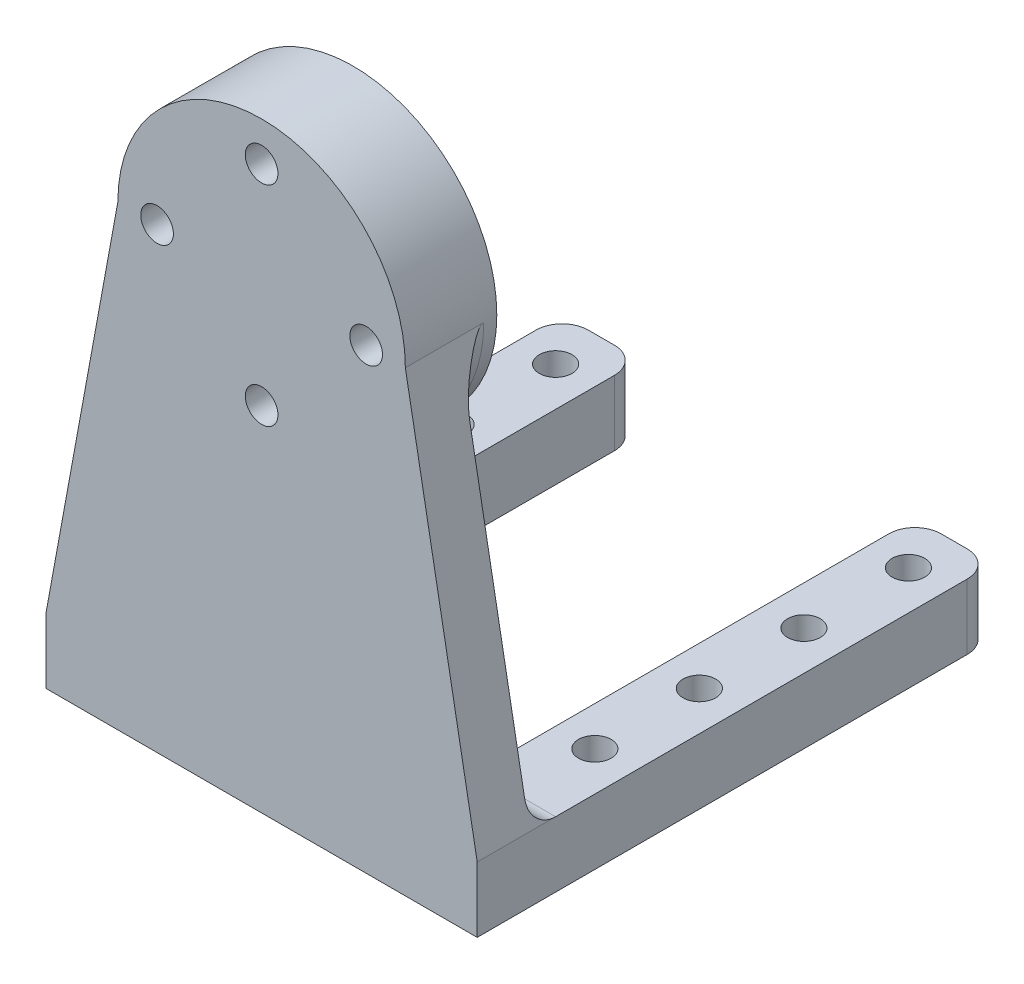
SolidWorks part; units mm, degrees
ref_plane "Plan de face" through (0, 0, 0) normal (0, 0, 1) x (1, 0, 0)
ref_plane "Plan de dessus" through (0, 0, 0) normal (0, 1, 0) x (1, 0, 0)
ref_plane "Plan de droite" through (0, 0, 0) normal (1, 0, 0) x (0, 0, -1)
sketch "Esquisse1" plane through (0, 0, 0) normal (0, 0, 1) x (1, 0, 0)
  circle A0 centre (0, 0) radius 11
  dimension "D1" = 22
extrude "Boss.-Extru.1" add sketch "Esquisse1" along normal blind 7
sketch "Esquisse2" plane through (0, 0, 7) normal (0, 0, 1) x (1, 0, 0)
  line L0 (0, 0) -> (8, 0) construction
  circle A0 centre (8, 0) radius 1.25
  circle A1 centre (0, -8) radius 1.25
  circle A2 centre (-8, 0) radius 1.25
  circle A3 centre (0, 8) radius 1.25
  point P13 (0, 0)
  dimension "D2" = 2.5
  dimension "D1" = 8
extrude "Enlèv. mat.-Extru.1" cut sketch "Esquisse2" against normal through all
sketch "Esquisse3" plane through (0, 0, 7) normal (0, 0, 1) x (1, 0, 0)
  line L0 (-11, 0) -> (-11, -35) construction
  line L1 (-11, -35) -> (11, -35)
  line L2 (11, -35) -> (11, 0) construction
  line L4 (-16.5, -35) -> (-11, -35)
  line L5 (11, -35) -> (16.5, -35)
  line L7 (-16.5, -35) -> (-16.5, -30)
  line L8 (-16.5, -30) -> (-11, 0)
  line L9 (11, 0) -> (16.5, -30)
  line L10 (16.5, -30) -> (16.5, -35)
  circle A0 centre (0, 0) radius 11 construction
  arc A1 (-11, 0) -> (11, 0) centre (0, 0) ccw
  dimension "D1" = 35
  dimension "D2" = 5.5
  dimension "D3" = 5
extrude "Boss.-Extru.2" add sketch "Esquisse3" against normal blind 4
sketch "Esquisse5" plane through (0, 0, 3) normal (0, 0, -1) x (-1, 0, 0)
  line L0 (16.5, -35) -> (-16.5, -35) construction
  line L1 (-16.5, -30) -> (-10.5, -30)
  line L2 (-16.5, -30) -> (-16.5, -35)
  line L3 (-16.5, -35) -> (-10.5, -35)
  line L4 (-10.5, -30) -> (-10.5, -35)
  line L6 (16.5, -30) -> (10.5, -30)
  line L7 (16.5, -30) -> (16.5, -35)
  line L8 (16.5, -35) -> (10.5, -35)
  line L9 (10.5, -30) -> (10.5, -35)
  dimension "D1" = 6
extrude "Boss.-Extru.3" add sketch "Esquisse5" along normal blind 35.5
sketch "Esquisse6" plane through (0, -30, 0) normal (0, 1, 0) x (1, 0, 0)
  line L0 (13.5, -3) -> (13.5, 32.5) construction
  line L1 (10.5, -3) -> (16.5, -3) construction
  line L2 (10.5, 32.5) -> (16.5, 32.5) construction
  line L3 (0, 0) -> (0, 6.48) construction
  circle A0 centre (13.5, 5) radius 1.25
  circle A1 centre (13.5, 13) radius 1.25
  circle A2 centre (13.5, 21) radius 1.25
  circle A3 centre (13.5, 29) radius 1.25
  circle A4 centre (-13.5, 29) radius 1.25
  circle A5 centre (-13.5, 21) radius 1.25
  circle A6 centre (-13.5, 5) radius 1.25
  circle A7 centre (-13.5, 13) radius 1.25
  dimension "D2" = 2.5
  dimension "D1" = 8
extrude "Enlèv. mat.-Extru.2" cut sketch "Esquisse6" against normal through all
fillet "Congé1" radius 2 9 edges at (-16.5, -32.5, -32.5) (-10.5, -32.5, -32.5) (10.5, -32.5, -32.5) (16.5, -32.5, -32.5) (0, -11, 3) (-10.5, -32.5, 3) (-13.5, -30, 3) (10.5, -32.5, 3) (13.5, -30, 3)
